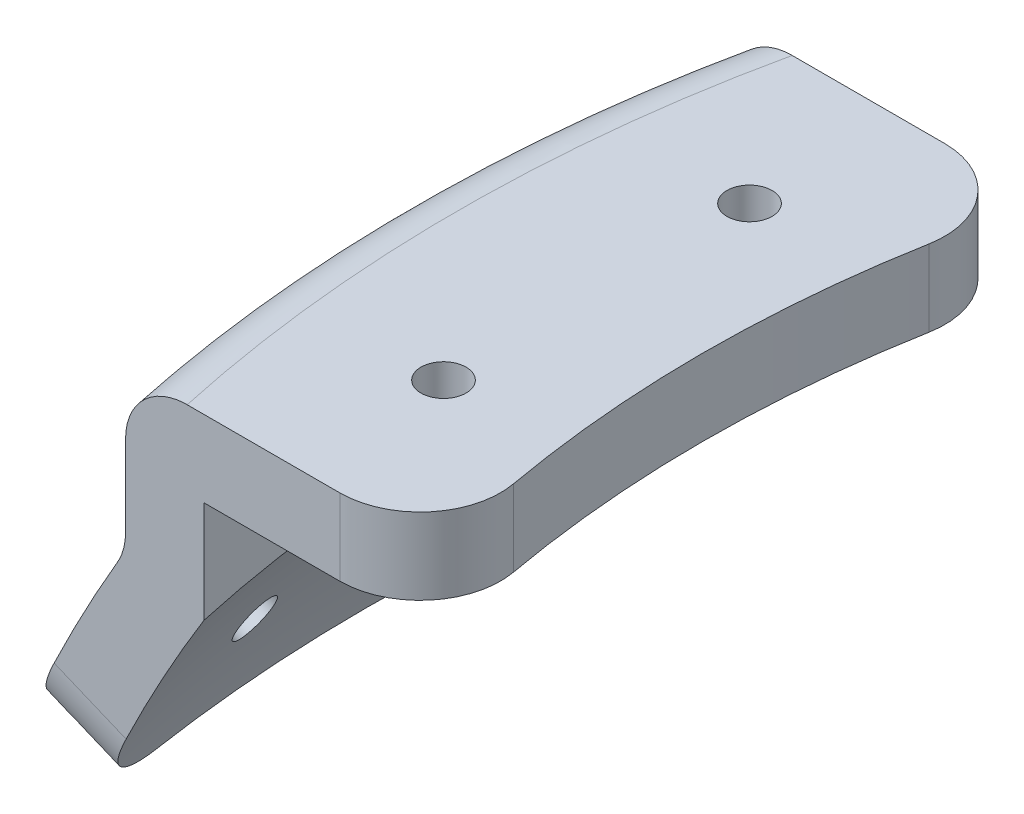
SolidWorks part; units mm, degrees
material "Polyether Polyol"
ref_plane "Front Plane" through (0, 0, 0) normal (0, 0, 1) x (1, 0, 0)
ref_plane "Top Plane" through (0, 0, 0) normal (0, 1, 0) x (1, 0, 0)
ref_plane "Right Plane" through (0, 0, 0) normal (1, 0, 0) x (0, 0, -1)
sketch "Sketch2" plane through (0, 0, 0) normal (0, 0, 1) x (1, 0, 0)
  line L0 (-196.1445, 172.2241) -> (-187.3619, 168.5374) construction
  line L1 (-183.6262, 216.8935) -> (-183.6262, 197.2811) construction
  line L2 (-174.1012, 207.3685) -> (-174.1012, 194.6685) construction
  line L3 (-145.5262, 207.3685) -> (-174.1012, 207.3685) construction
  line L4 (-145.5262, 207.3685) -> (-145.5262, 216.8935) construction
  line L5 (-145.5262, 216.8935) -> (-183.6262, 216.8935) construction
  line L6 (-196.1445, 172.2241) -> (-187.3619, 168.5374)
  line L7 (-183.6262, 216.8935) -> (-183.6262, 197.2811)
  line L8 (-174.1012, 207.3685) -> (-174.1012, 194.6685)
  line L9 (-145.5262, 207.3685) -> (-174.1012, 207.3685)
  line L10 (-145.5262, 207.3685) -> (-145.5262, 216.8935)
  line L11 (-145.5262, 216.8935) -> (-183.6262, 216.8935)
  line L12 (0, 0) -> (0, 215.8974) construction
  arc A0 (-183.6262, 197.2811) -> (-196.1445, 172.2241) centre (0, 89.8878) ccw construction
  arc A1 (-174.1012, 194.6685) -> (-187.3619, 168.5374) centre (0, 89.8878) ccw construction
  arc A2 (-183.6262, 197.2811) -> (-196.1445, 172.2241) centre (0, 89.8878) ccw
  arc A3 (-174.1012, 194.6685) -> (-187.3619, 168.5374) centre (0, 89.8878) ccw
revolve "Revolve1" add sketch "Sketch2" angle 30 mid plane about L12
fillet "Fillet1" radius 7.5 2 edges at (-183.6262, 197.2811, 0) (-183.6262, 216.8935, 0)
sketch "Sketch3" plane through (0, 207.3685, 0) normal (0, -1, 0) x (1, 0, 0)
  circle A0 centre (-158.75, 19.05) radius 3.5719 construction
  circle A1 centre (-158.75, -19.05) radius 3.5719 construction
  circle A2 centre (-158.75, 19.05) radius 3.5719 construction
  circle A3 centre (-158.75, -19.05) radius 3.5719 construction
  circle A4 centre (-158.75, -19.05) radius 2.805
  circle A5 centre (-158.75, 19.05) radius 2.805
  dimension "D1" = 5.61
extrude "Cut-Extrude1" cut sketch "Sketch3" against normal through all both and the other way through all
sketch "Sketch4" plane through (0, 216.8935, 0) normal (0, 1, 0) x (1, 0, 0)
  line L1 (-140.5675, 37.665) -> (-215.4275, 37.665)
  line L2 (-140.5675, 37.665) -> (-140.5675, -37.665)
  line L3 (-140.5675, -37.665) -> (-215.4275, -37.665)
  line L4 (-215.4275, 37.665) -> (-215.4275, -37.665)
extrude "Cut-Extrude2" cut sketch "Sketch4" against normal through all flip side to cut
fillet "Fillet2" radius 10 4 edges at (-140.5675, 212.131, -37.665) (-140.5675, 212.131, 37.665)
sketch "Sketch5" plane through (0, 0, 0) normal (0, 0, 1) x (1, 0, 0)
  line L0 (0, 89.8878) -> (-181.0525, 182.1386) construction
  line L1 (0, 0) -> (0, 215.8974) construction
  arc A1 (-174.1012, 194.6685) -> (-187.3619, 168.5374) centre (0, 89.8878) ccw construction
  dimension "D1" = 63
ref_plane "Plane1" through (36.3604, 71.3612, 0) normal (0.454, 0.891, 0) x (-0.891, 0.454, 0)
sketch "Sketch6" plane through (36.3604, 71.3612, 0) normal (0.454, 0.891, 0) x (-0.891, 0.454, 0)
  line L0 (216.8377, 18.9708) -> (270.6406, 23.678) construction
  line L1 (40.8082, 0) -> (244.0082, 0) construction
  line L2 (216.8377, 18.9708) -> (271.2422, 23.7306)
  line L3 (216.8377, 18.9708) -> (216.5932, 21.7652)
  line L4 (271.2422, 23.7306) -> (270.9977, 26.5249)
  line L5 (216.5932, 21.7652) -> (270.9977, 26.5249)
  dimension "D1" = 5
  dimension "D2" = 2.805
revolve "Cut-Revolve1" cut sketch "Sketch6" angle 360 about L0
mirror "Mirror1" about plane through (0, 0, 0) normal (0, 0, 1) of "Cut-Revolve1"
